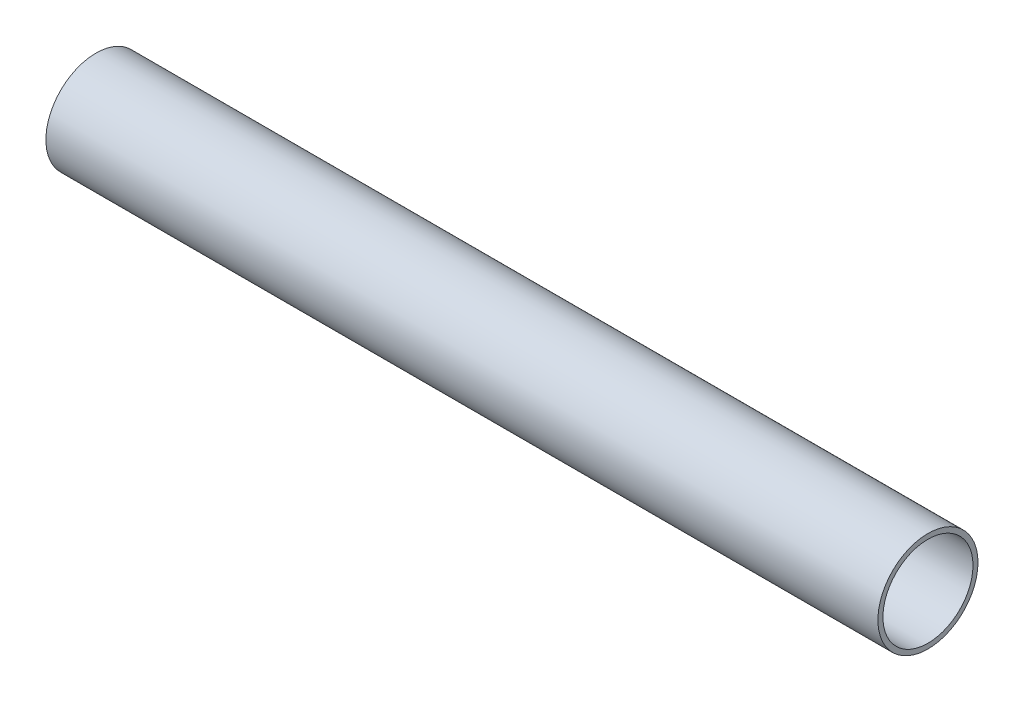
SolidWorks part; units mm, degrees
material "PC High Viscosity"
ref_plane "Front Plane" through (0, 0, 0) normal (0, 0, 1) x (1, 0, 0)
ref_plane "Top Plane" through (0, 0, 0) normal (0, 1, 0) x (1, 0, 0)
ref_plane "Right Plane" through (0, 0, 0) normal (1, 0, 0) x (0, 0, -1)
sketch "Sketch1" plane through (0, 0, 0) normal (1, 0, 0) x (0, 0, -1)
  circle A0 centre (0, 0) radius 15.875
  dimension "D1" = 31.75
extrude "Extrude-Thin1" add sketch "Sketch1" along normal mid plane 263.9115 thin thin type one direction reverse wall 1.5875
